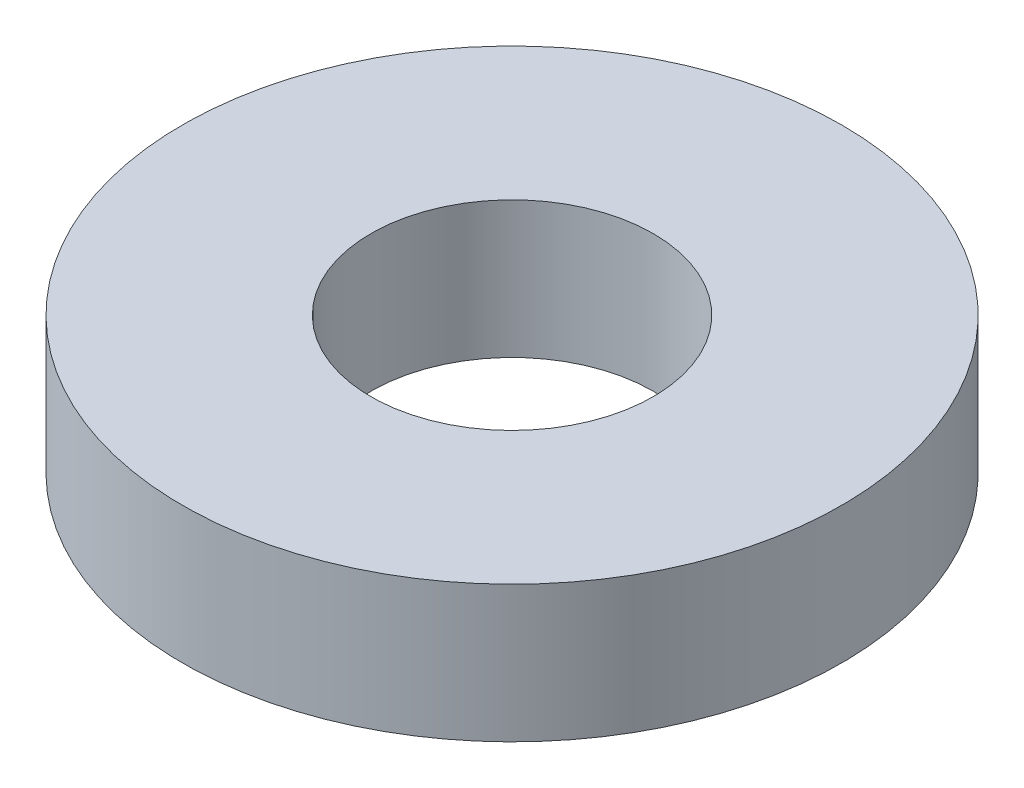
SolidWorks part; units mm, degrees
ref_plane "Front Plane" through (0, 0, 0) normal (0, 0, 1) x (1, 0, 0)
ref_plane "Top Plane" through (0, 0, 0) normal (0, 1, 0) x (1, 0, 0)
ref_plane "Right Plane" through (0, 0, 0) normal (1, 0, 0) x (0, 0, -1)
sketch "Sketch1" plane through (0, 0, 0) normal (0, 1, 0) x (1, 0, 0)
  circle A0 centre (0, 0) radius 70
  dimension "FLANGE_OD" = 140
extrude "Boss-Extrude1" add sketch "Sketch1" along normal blind 29
sketch "Sketch2" plane through (0, 0, 0) normal (0, 1, 0) x (1, 0, 0)
  circle A0 centre (0, 0) radius 30
  dimension "BORE_D" = 60
extrude "Cut-Extrude1" cut sketch "Sketch2" along normal through all
sketch "Sketch3" plane through (0, 29, 0) normal (0, 1, 0) x (1, 0, 0)
  circle A0 centre (0, 0) radius 21.6818 construction
  circle A1 centre (-21.6818, 0) radius 2.8084
  dimension "BOLT_D" = 5.6168
  dimension "BOLT_PCD" = 43.3637
extrude "Cut-Extrude2" cut sketch "Sketch3" against normal blind 17.9458 rebuild error yes
pattern_circular "CirPattern1" count 3 over 360 rebuild error yes
